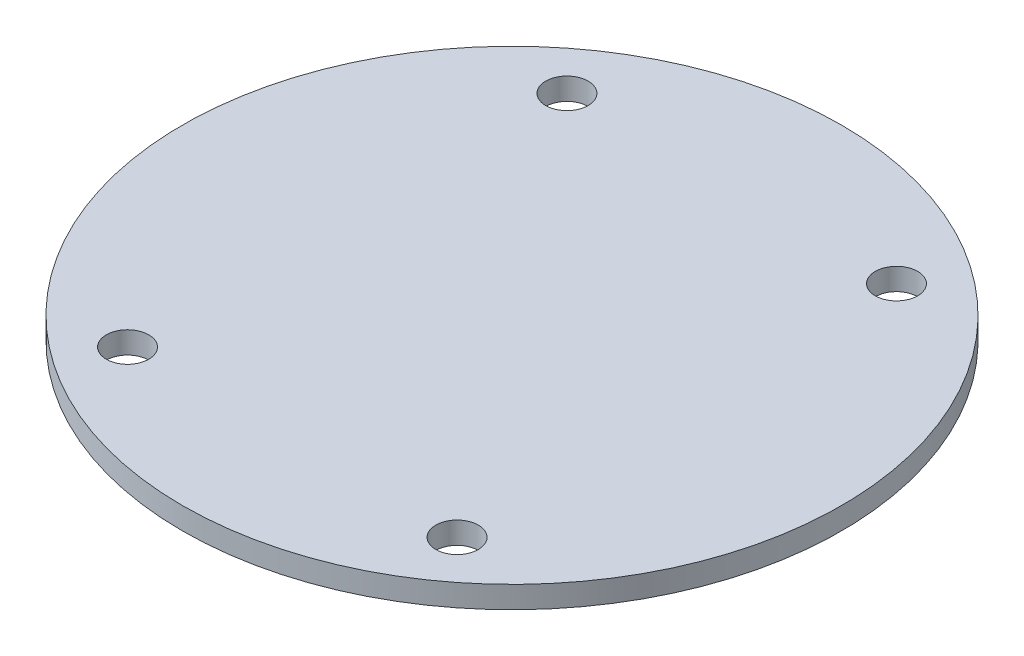
SolidWorks part; units mm, degrees
material "Epoxy, Unfilled"
ref_plane "Front Plane" through (0, 0, 0) normal (0, 0, 1) x (1, 0, 0)
ref_plane "Top Plane" through (0, 0, 0) normal (0, 1, 0) x (1, 0, 0)
ref_plane "Right Plane" through (0, 0, 0) normal (1, 0, 0) x (0, 0, -1)
ref_axis "x-axis" through (88.99, 0, 0) along (-1, 0, 0)
ref_axis "y-axis" through (0, 0, 55) along (0, 0, -1)
ref_axis "z-axis" through (0, 55, 0) along (0, -1, 0)
sketch "Sketch2" plane through (0, 0, 0) normal (0, 1, 0) x (1, 0, 0)
  circle A0 centre (0, 0) radius 30
  dimension "D1" = 60
extrude "AcrylicBase" add sketch "Sketch2" against normal blind 2
hole_wizard "#24 (0.152) Diameter Hole1" positions "Sketch8" profile "Sketch7" hole size "#24" standard "Ansi Inch"
sketch "Sketch8" plane through (0, 0, 0) normal (0, 1, 0) x (-1, 0, 0)
  line L0 (15, -20) -> (-15, -20) construction
  line L1 (-15, -20) -> (-15, 20) construction
  line L2 (-15, 20) -> (15, 20) construction
  line L3 (15, 20) -> (15, -20) construction
  line L5 (15, 0) -> (-15, 0) construction
  line L7 (0, -20) -> (0, 20) construction
  point P0 (15, -20)
  point P1 (-15, -20)
  point P2 (-15, 20)
  point P4 (15, 20)
  dimension "D1" = 30
  dimension "D2" = 40
sketch "Sketch7" plane through (-15, 0, -20) normal (1, 0, 0) x (0, 0, 1)
  line L0 (0, 0) -> (0, 26.5599)
  line L1 (0, 26.5599) -> (1.9304, 25.4)
  line L2 (1.9304, 25.4) -> (1.9304, 0)
  line L5 (1.9304, 0) -> (0, 0)
  line L10 (0, 26.5599) -> (-1.9304, 25.4) construction
  line L11 (0, -6.35) -> (0, 107.95) construction
  dimension "Hole Dia." = 3.8608
  dimension "Hole Depth" = 25.4
  dimension "Drill Angle" = 118
